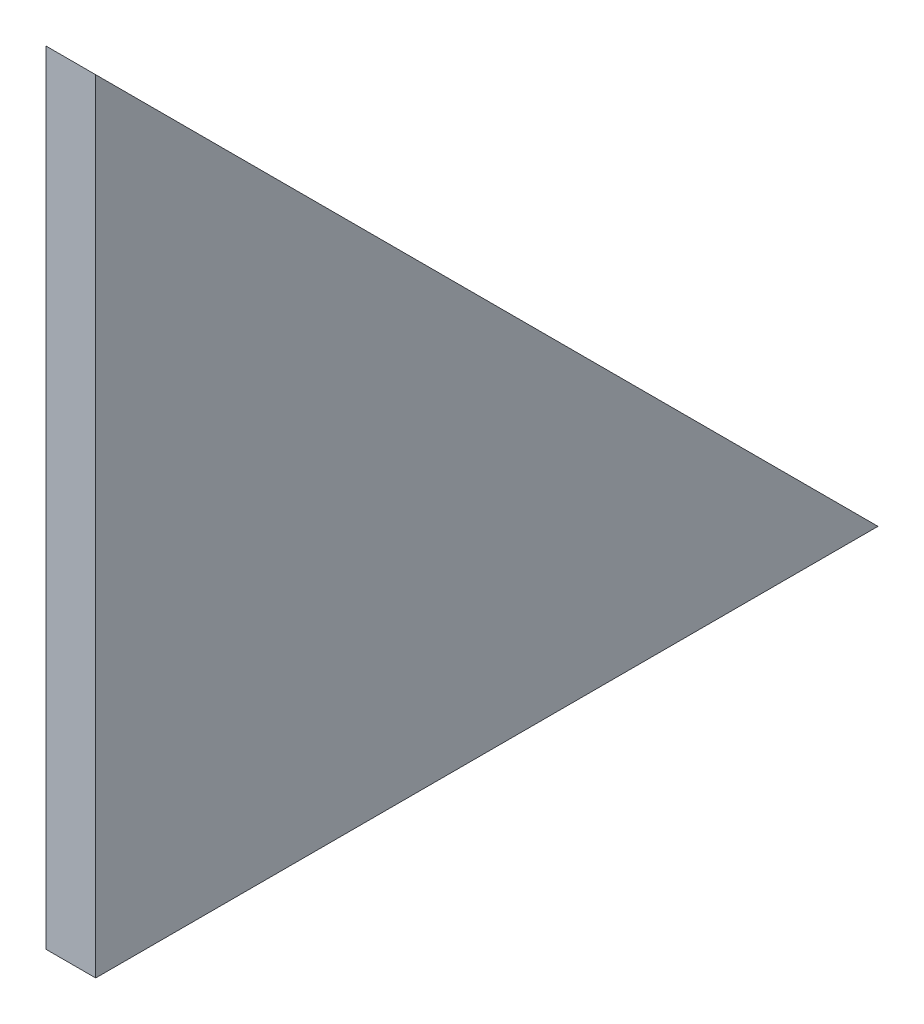
SolidWorks part; units mm, degrees
material "Acero al carbono no aleado"
ref_plane "Alzado" through (0, 0, 0) normal (0, 0, 1) x (1, 0, 0)
ref_plane "Planta" through (0, 0, 0) normal (0, 1, 0) x (1, 0, 0)
ref_plane "Vista lateral" through (0, 0, 0) normal (1, 0, 0) x (0, 0, -1)
sketch "Croquis1" plane through (0, 0, 0) normal (0, 0, 1) x (1, 0, 0)
  line L1 (3.175, -50) -> (-3.175, -50)
  line L2 (3.175, -50) -> (3.175, 50)
  line L3 (3.175, 50) -> (-3.175, 50)
  line L4 (-3.175, -50) -> (-3.175, 50)
  line L5 (3.175, -50) -> (-3.175, 50) construction
  line L6 (3.175, 50) -> (-3.175, -50) construction
  line L8 (-3.175, -50) -> (-3.175, -47)
  point P0 (0, 0)
  dimension "D1" = 6.35
  dimension "D4" = 100
extrude "Saliente-Extruir1" add sketch "Croquis1" along normal mid plane 100 contours L4 L1 L2 L3
sketch "Croquis3" plane through (-3.175, 0, 0) normal (-1, 0, 0) x (0, 0, 1)
  line L0 (50, 50) -> (-50, -50)
  line L4 (-50, -50) -> (50, -50)
  line L5 (50, -50) -> (50, 50)
  line L6 (50, 50) -> (-50, 50)
  line L7 (-50, 50) -> (-50, -50)
  line L9 (50, -50) -> (50, 50)
  line L10 (50, 50) -> (-50, 50)
  line L11 (-50, 50) -> (-50, -50)
  line L13 (-50, -50) -> (50, -50)
  line M7 (50, 50) -> (-50, 50)
  line M8 (-50, 50) -> (-50, -50)
  dimension "D1" = 0
extrude "Cortar-Extruir2" cut sketch "Croquis3" against normal blind 100 contours L0 M7 M8 region at (-3.175, 16.6667, -16.6667)
